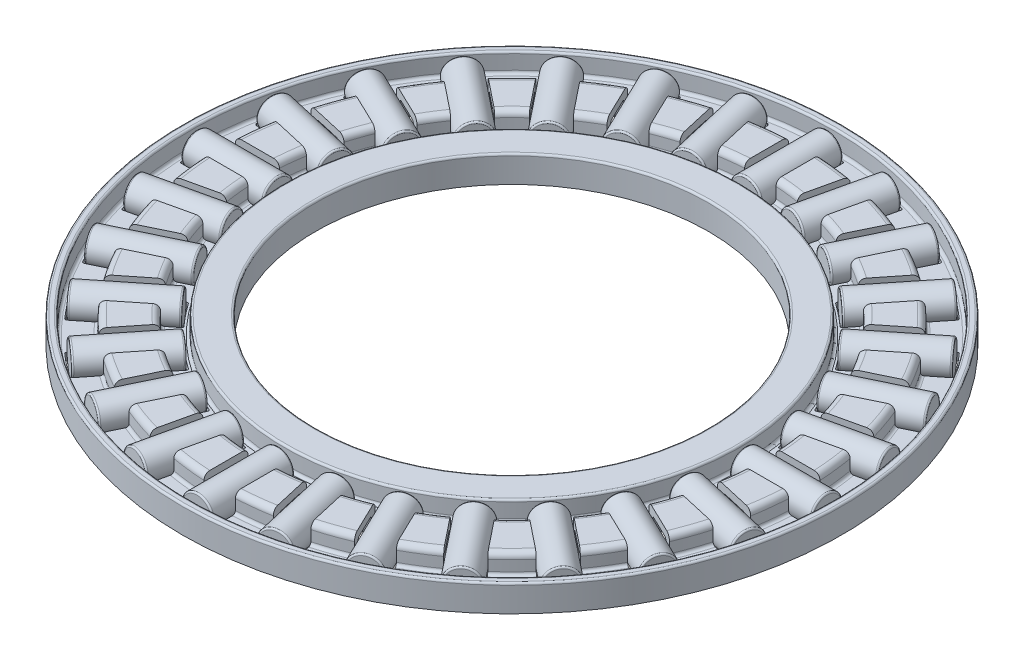
SolidWorks part; units mm, degrees
ref_plane "Front Plane" through (0, 0, 0) normal (0, 0, 1) x (1, 0, 0)
ref_plane "Top Plane" through (0, 0, 0) normal (0, 1, 0) x (1, 0, 0)
ref_plane "Right Plane" through (0, 0, 0) normal (1, 0, 0) x (0, 0, -1)
sketch "Sketch1" plane through (0, 0, 0) normal (1, 0, 0) x (0, 0, -1)
  line L0 (-21, 0) -> (21, 0) construction
  line L1 (-12.52, 0) -> (12.52, 0) construction
  line L2 (21, -1) -> (21, 1) construction
  line L3 (12.52, -0.85) -> (12.52, 0.85) construction
  line L4 (12.52, -0.85) -> (13.18, -0.85) construction
  line L5 (13.18, -0.85) -> (13.18, 0.3726) construction
  line L6 (13.18, 0.3726) -> (13.84, 0.3726) construction
  line L7 (13.84, 0.3726) -> (13.84, -0.85) construction
  line L8 (13.84, -0.85) -> (16.3303, -0.85) construction
  line L9 (16.3303, -0.85) -> (16.3303, 0.3726) construction
  line L10 (16.3303, 0.3726) -> (18.1764, 0.3726) construction
  line L11 (18.1764, 0.3726) -> (18.1764, -0.85) construction
  line L12 (18.1764, -0.85) -> (20.6667, -0.85) construction
  line L13 (20.6667, -0.85) -> (20.6667, 0.3726) construction
  line L14 (20.6667, 0.3726) -> (20.8333, 0.3726) construction
  line L15 (12.52, 0.85) -> (14.5, 0.85) construction
  line L16 (14.5, 0.85) -> (14.5, -0.3726) construction
  line L17 (14.5, -0.3726) -> (15.8528, -0.3726) construction
  line L18 (15.8528, -0.3726) -> (15.8528, 0.85) construction
  line L19 (15.8528, 0.85) -> (18.6538, 0.85) construction
  line L20 (18.6538, 0.85) -> (18.6538, -0.3726) construction
  line L21 (18.6538, -0.3726) -> (20.5, -0.3726) construction
  line L22 (20.5, -0.3726) -> (20.5, 0.85) construction
  line L23 (20.5, 0.85) -> (21, 0.85) construction
  line L24 (16.3303, 0.3726) -> (15.8528, 0.3726) construction
  line L25 (13.84, 0.3726) -> (13.84, 0.85) construction
  line L26 (18.1764, 0.3726) -> (18.6538, 0.3726) construction
  line L27 (14.5, -0.3726) -> (14.5, -0.85) construction
  line L28 (14.5, -0.3726) -> (13.84, -0.3726) construction
  line L29 (20.6667, 0.3726) -> (20.5, 0.3726) construction
  line L30 (20.8333, 0.3726) -> (20.8333, -0.85) construction
  line L31 (20.8333, -0.85) -> (21, -0.85) construction
  line L32 (0, 1) -> (0, -1) construction
  line L33 (-14.5, 1) -> (14.5, 1) construction
  line L34 (-20.5, 0.85) -> (20.5, 0.85) construction
  line L35 (20.8333, 0.3726) -> (21, 0.3726) construction
  line L36 (15.8528, -0.3726) -> (15.8528, -0.85) construction
  line L37 (18.1764, 0.3726) -> (18.1764, 0.85) construction
  line L38 (13.18, -0.3726) -> (12.52, -0.3726) construction
  line L39 (13.84, -0.3726) -> (13.18, -0.3726) construction
  point P4 (0, 0)
  point P8 (0, 0)
  point P11 (21, 0)
  point P14 (12.52, 0)
  point P45 (0, 1)
  point P48 (0, 0)
  point P49 (0, 1)
  point P55 (0, 0.85)
  dimension "OD" = 42
  dimension "ID" = 25.04
  dimension "Thickness" = 2
  dimension "Approx. Raceway Thickness" = 1.7
  dimension "Inner Raceway" = 29
  dimension "Outer Raceway" = 41
  dimension "Approx. Raceway Notch Width" = 1.8462
  dimension "D3" = 1.8462
sketch "Sketch2" plane through (0, 0, 0) normal (0, 1, 0) x (1, 0, 0)
  line L0 (14.5, 0) -> (20.5, 0) construction
  line L1 (20.2, 0) -> (14.8, 0)
  line L2 (20.1752, -1) -> (14.7662, -1)
  line L3 (20.1752, 1) -> (14.7662, 1)
  circle A0 centre (0, 0) radius 12.52
  circle A1 centre (0, 0) radius 14.5
  circle A2 centre (0, 0) radius 20.5
  circle A3 centre (0, 0) radius 21
  arc A4 (14.7662, -1) -> (14.7662, 1) centre (0, 0) ccw
  arc A5 (20.1752, -1) -> (20.1752, 1) centre (0, 0) ccw
  arc A6 (20.1752, 1) -> (20.0061, 2.7922) centre (0, 0) ccw
  point P15 (17.5, 0)
  dimension "Approx. Roller Length" = 5.4
  dimension "Roller Thickness" = 2
  dimension "Roller Arc Length" = 2.0008
  dimension "Approx. Roller Gap" = 1.8007
sketch "Sketch3" plane through (0, 0, 0) normal (1, 0, 0) x (0, 0, -1)
  line L0 (13.18, -0.85) -> (13.18, 0.3726)
  line L1 (13.18, 0.3726) -> (13.84, 0.3726)
  line L2 (13.84, 0.3726) -> (13.84, -0.85)
  line L3 (13.84, -0.85) -> (16.3303, -0.85)
  line L4 (16.3303, -0.85) -> (16.3303, 0.3726)
  line L5 (16.3303, 0.3726) -> (18.1764, 0.3726)
  line L6 (18.1764, 0.3726) -> (18.1764, -0.85)
  line L7 (18.1764, -0.85) -> (20.6667, -0.85)
  line L8 (20.6667, -0.85) -> (20.6667, 0.3726)
  line L9 (20.6667, 0.3726) -> (20.8333, 0.3726)
  line L10 (20.8333, 0.3726) -> (20.8333, -0.85)
  line L11 (20.8333, -0.85) -> (21, -0.85)
  line L12 (21, -0.85) -> (21, 0.85)
  line L13 (21, 0.85) -> (20.5, 0.85)
  line L14 (20.5, 0.85) -> (20.5, -0.3726)
  line L15 (20.5, -0.3726) -> (18.6538, -0.3726)
  line L16 (18.6538, -0.3726) -> (18.6538, 0.85)
  line L17 (18.6538, 0.85) -> (15.8528, 0.85)
  line L18 (15.8528, 0.85) -> (15.8528, -0.3726)
  line L19 (15.8528, -0.3726) -> (14.5, -0.3726)
  line L20 (14.5, -0.3726) -> (14.5, 0.85)
  line L21 (14.5, 0.85) -> (12.52, 0.85)
  line L22 (12.52, 0.85) -> (12.52, -0.85)
  line L23 (12.52, -0.85) -> (13.18, -0.85)
revolve "Revolve1" add sketch "Sketch3" angle 360 about L32
fillet "Fillet1" radius 0.3692 4 edges at (0, -0.85, 18.1764) (0, -0.85, 20.6667) (0, -0.85, 13.84) (0, -0.85, 16.3303)
fillet "Fillet2" radius 0.3692 2 edges at (0, 0.85, 18.6538) (0, 0.85, 15.8528)
fillet "Fillet3" radius 0.125 4 edges at (0, 0.85, 20.5) (0, 0.85, 21) (0, 0.85, 14.5) (0, 0.85, 12.52)
fillet "Fillet4" radius 0.1846 6 edges at (0, 0.3726, 16.3303) (0, 0.3726, 18.1764) (0, -0.3726, 20.5) (0, -0.3726, 18.6538) (0, -0.3726, 15.8528) (0, -0.3726, 14.5)
sketch "Sketch4" plane through (0, 0, 0) normal (0, 1, 0) x (1, 0, 0)
  line L0 (14.7662, 1) -> (20.1752, 1)
  line L1 (14.7662, -1) -> (20.1752, -1)
  arc A0 (14.7662, -1) -> (14.7662, 1) centre (0, 0) ccw construction
  arc A1 (14.7662, -1) -> (14.7662, 1) centre (0, 0) ccw
  arc A2 (20.1752, -1) -> (20.1752, 1) centre (0, 0) ccw construction
  arc A3 (20.1752, -1) -> (20.1752, 1) centre (0, 0) ccw
extrude "Cut-Extrude1" cut sketch "Sketch4" against normal through all both and the other way through all
fillet "Fillet5" radius 0.1 4 edges at (20.1752, -0.6113, -1) (20.1752, -0.6113, 1) (14.7662, -0.6113, -1) (14.7662, -0.6113, 1)
pattern_circular "CirPattern1" count 28 over 360 about axis through (0, 1, 0) along (0, -1, 0) of "Cut-Extrude1", "Fillet5"
sketch "Sketch5" plane through (0, 0, 0) normal (0, 1, 0) x (1, 0, 0)
  line L0 (14.8728, 0) -> (14.8728, 1)
  line L2 (14.8728, 1) -> (20.0798, 1)
  line L3 (20.0798, 1) -> (20.0798, 0)
  line L4 (20.0798, 0) -> (14.8728, 0)
  line L5 (20.2, 0) -> (14.8, 0) construction
revolve "Revolve2" add sketch "Sketch5" angle 360 about L1
fillet "Fillet6" radius 0.1 2 edges at (14.8728, 0, -1) (20.0798, 0, -1)
pattern_circular "CirPattern2" count 28 over 360 about axis through (0, 1, 0) along (0, -1, 0) of bodies 107
ref_axis "Center Axis 1" through (0, 1.65, 0) along (0, -1, 0)
ref_plane "Contact Plane 1" through (0, 1, 0) normal (0, 1, 0) x (1, 0, 0)
ref_plane "Contact Plane 2" through (0, -1, 0) normal (0, 1, 0) x (1, 0, 0)
equation "\"Approx. Raceway Thickness@Sketch1\" = \"Thickness@Sketch1\" * .85"
equation "\"Approx. Raceway Notch Width@Sketch1\" =  ( \"Outer Raceway@Sketch1\" - \"Inner Raceway@Sketch1\" )  / 6.5"
equation "\"D3@Sketch1\" = \"Approx. Raceway Notch Width@Sketch1\""
equation "\"D1@Fillet2\"=\"D1@Fillet1\""
equation "\"D1@Fillet3\"=(\"OD@Sketch1\"-\"Outer Raceway@Sketch1\")/8"
equation "\"D1@Fillet1\" = \"Approx. Raceway Notch Width@Sketch1\" * 2 / 10"
equation "\"D1@Fillet4\"=\"D1@Fillet2\"/2"
equation "\"Approx. Roller Length@Sketch2\" =  ( \"Outer Raceway@Sketch1\" - \"Inner Raceway@Sketch1\" )  / 2 * .9"
equation "\"Approx. Roller Gap@Sketch2\" = \"Roller Arc Length@Sketch2\" * .9"
equation "\"Raceway Diff\"= ( \"Outer Raceway@Sketch1\" - \"Inner Raceway@Sketch1\" )"
equation "\"Circumference\"= ( \"Inner Raceway@Sketch1\" + ( \"Raceway Diff\" / 2 ) ) * 3.14"
equation "\"Instances\"= int ( \"Circumference\" /  ( \"Roller Arc Length@Sketch2\" + \"Approx. Roller Gap@Sketch2\" )  ) "
equation "\"D1@CirPattern1\"=\"Instances\""
equation "\"D1@Fillet5\" = \"Roller Arc Length@Sketch2\" / 20"
equation "\"D1@Fillet6\" = \"Roller Arc Length@Sketch2\" / 20"
equation "\"D1@CirPattern2\" = \"D1@CirPattern1\""
equation "\"Roller Thickness@Sketch2\" = \"Thickness@Sketch1\""
